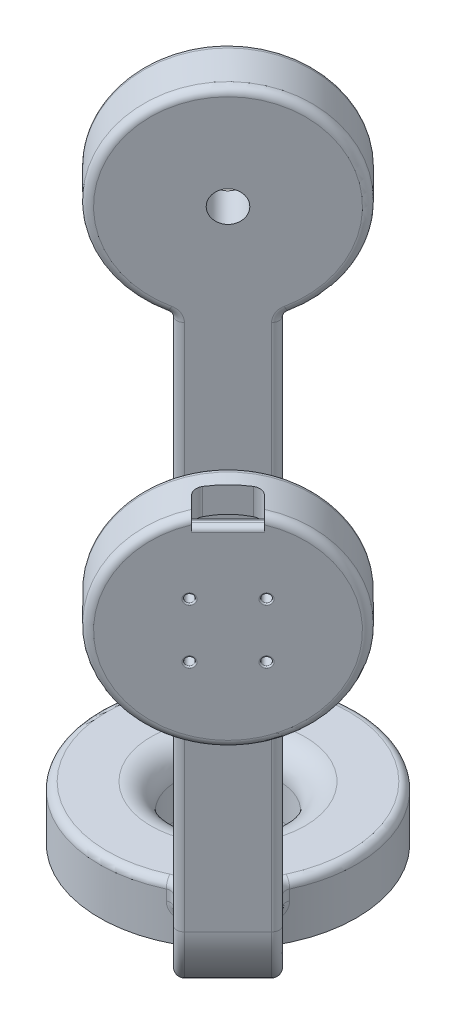
SolidWorks part; units mm, degrees
ref_plane "前视基准面" through (0, 0, 0) normal (0, 0, 1) x (1, 0, 0)
ref_plane "上视基准面" through (0, 0, 0) normal (0, 1, 0) x (1, 0, 0)
ref_plane "右视基准面" through (0, 0, 0) normal (1, 0, 0) x (0, 0, -1)
other "Configuration Table"
sketch "草图2" plane through (0, 0, 0) normal (0, 0, 1) x (1, 0, 0)
  line L2 (33, -6) -> (50, -6)
  line L3 (50, -6) -> (50, 5)
  line L9 (50, 5) -> (50, 14)
  line L10 (50, 14) -> (30, 14)
  line L15 (0, -22) -> (25, -22)
  line L17 (25, -22) -> (27, -22)
  line L18 (30, -19) -> (30, -9)
  line L19 (0, -22) -> (0, -12)
  line L20 (0, -12) -> (17, -12)
  line L21 (30, -9) -> (30, -6)
  line L22 (30, -6) -> (33, -6)
  line L23 (20, 4) -> (20, -9)
  arc A0 (27, -22) -> (30, -19) centre (27, -19) ccw
  arc A3 (20, -9) -> (17, -12) centre (17, -9) cw
  arc A4 (30, 14) -> (20, 4) centre (30, 4) ccw
  dimension "D1" = 3
  dimension "D2" = 10
revolve "旋转1" add sketch "草图2" angle 360 about L19
sketch "草图3" plane through (0, 0, 0) normal (0, -1, 0) x (1, 0, 0)
  circle A0 centre (12.5, 0) radius 1.6
  circle A1 centre (0, -12.5) radius 1.6
  circle A2 centre (-12.5, 0) radius 1.6
  circle A3 centre (0, 12.5) radius 1.6
  point P13 (0, 0)
  dimension "D1" = 4
extrude "切除-拉伸1" cut sketch "草图3" along normal blind 94
sketch "草图6" plane through (0, 0, 0) normal (-0.7071, 0, 0.7071) x (0.7071, 0, 0.7071)
  line L0 (30, 14) -> (30, 4)
  line L1 (0, 0) -> (0, 30.9502)
  line L3 (-30, 14) -> (-30, 4)
  line L5 (50, 14) -> (70, 14)
  line L8 (90, 34) -> (90, 114)
  line L13 (50, 14) -> (30, 14)
  line L17 (90, 114) -> (100, 114)
  line L18 (100, 114) -> (100, 34)
  line L19 (70, 4) -> (30, 4)
  line L20 (-50, 14) -> (-30, 14)
  line L21 (-70, 4) -> (-30, 4)
  line L22 (-50, 14) -> (-70, 14)
  line L23 (-90, 34) -> (-90, 114)
  line L24 (-90, 114) -> (-100, 114)
  line L25 (-100, 114) -> (-100, 34)
  arc A0 (90, 34) -> (70, 14) centre (70, 34) cw
  arc A2 (100, 34) -> (70, 4) centre (70, 34) cw
  arc A3 (-90, 34) -> (-70, 14) centre (-70, 34) ccw
  arc A4 (-100, 34) -> (-70, 4) centre (-70, 34) ccw
  dimension "D1" = 20
  dimension "D2" = 30
  dimension "D3" = 20
  dimension "D4" = 40
  dimension "D5" = 80
sketch "草图7" plane through (0, 0, 0) normal (-0.7071, 0, 0.7071) x (0.7071, 0, 0.7071)
  line L10 (90, 114) -> (103, 114)
  line L11 (103, 114) -> (103, 119)
  line L12 (103, 119) -> (107, 119)
  line L13 (107, 119) -> (107, 144)
  line L14 (107, 144) -> (112, 144)
  line L15 (112, 144) -> (112, 104)
  line L16 (90, 114) -> (90, 104)
  line L17 (112, 104) -> (90, 104)
  line L18 (0, 30.9502) -> (0, 0)
  line L19 (-90, 114) -> (-90, 104)
  line L20 (-112, 104) -> (-90, 104)
  line L21 (-112, 144) -> (-112, 104)
  line L22 (-107, 144) -> (-112, 144)
  line L27 (-107, 144) -> (-90, 144)
  line L28 (-90, 144) -> (-90, 114)
revolve "旋转2" add sketch "草图7" angle 360 about L14 region at (73.8745, 117.0769, 73.8745)
sketch "草图8" plane through (75.6604, 0, 75.6604) normal (-0.7071, 0, -0.7071) x (-0.7071, 0, 0.7071)
  circle A0 centre (10.6066, 154.6066) radius 1.6
  circle A1 centre (10.6066, 133.3934) radius 1.6
  circle A2 centre (-10.6066, 133.3934) radius 1.6
  circle A3 centre (-10.6066, 154.6066) radius 1.6
  point P13 (0, 144)
  dimension "D2" = 3.2
  dimension "D3" = 4
extrude "切除-拉伸3" cut sketch "草图8" against normal blind 30
fillet "圆角5" radius 0.5 4 edges at (85.5646, 133.3934, 72.8273) (70.5646, 133.3934, 87.8273) (70.5646, 154.6066, 87.8273) (85.5646, 154.6066, 72.8273)
fillet "圆角7" radius 1 2 edges at (51.6188, 144, 94.0452) (55.1543, 144, 90.5097)
sketch "草图9" plane through (75.6604, 0, 75.6604) normal (-0.7071, 0, -0.7071) x (-0.7071, 0, 0.7071)
  line L0 (0, 144) -> (19.5212, 144)
ref_plane "基准面3" through (0, 144, 0) normal (0, -1, 0) x (-0.7071, 0, 0.7071)
sketch "草图10" plane through (0, 144, 0) normal (0, -1, 0) x (-0.7071, 0, 0.7071)
  line L0 (0, -107) -> (10, -107)
  line L1 (0, -107) -> (19.5212, -107) construction
  line L2 (10, -107) -> (10, -102)
  line L3 (7, -99) -> (-7, -99)
  line L4 (-10, -102) -> (-10, -107)
  line L5 (-10, -107) -> (0, -107)
  arc A0 (-7, -99) -> (-10, -102) centre (-7, -102) ccw
  arc A1 (7, -99) -> (10, -102) centre (7, -102) cw
  dimension "D1" = 3
extrude "切除-拉伸4" cut sketch "草图10" against normal blind 225
sketch "草图11" plane through (75.6604, 0, 75.6604) normal (-0.7071, 0, -0.7071) x (-0.7071, 0, 0.7071)
  line L0 (-10, 179) -> (-10, 182.7298)
  line L1 (-10, 179) -> (10, 179)
  line L2 (10, 182.7298) -> (10, 166.9129) construction
  line L3 (10, 179) -> (10, 182.7298)
  arc A0 (10, 182.7298) -> (-10, 182.7298) centre (0, 144) ccw
extrude "切除-拉伸5" cut sketch "草图11" against normal blind 225
fillet "圆角8" radius 2 1 edges at (75.6604, 179, 75.6604)
fillet "圆角9" radius 2 1 edges at (79.196, 179, 79.196)
revolve "旋转3" add sketch "草图7<3>" angle 360 about L22 region at (-71.4178, 124, -71.4178)
sketch "草图7<3>" plane through (0, 0, 0) normal (-0.7071, 0, 0.7071) x (0.7071, 0, 0.7071) same geometry as "草图7"
sketch "草图12" plane through (-79.196, 0, -79.196) normal (-0.7071, 0, -0.7071) x (-0.7071, 0, 0.7071)
  line L0 (0, 144) -> (0, 104) construction
  line L1 (-42.1172, 144) -> (42.1172, 144) construction
  circle A0 centre (0, 144) radius 16.5
extrude "切除-拉伸6" cut sketch "草图12" against normal blind 6
sketch "草图13" plane through (-74.9533, 0, -74.9533) normal (-0.7071, 0, -0.7071) x (-0.7071, 0, 0.7071)
  circle A0 centre (0, 144) radius 6
extrude "切除-拉伸7" cut sketch "草图13" against normal blind 45
sketch "草图14" plane through (-74.9533, 0, -74.9533) normal (-0.7071, 0, -0.7071) x (-0.7071, 0, 0.7071)
  line L0 (0, 144) -> (0, 155.5)
  circle A0 centre (0, 155.5) radius 1.4
  circle A1 centre (11.5, 144) radius 1.4
  circle A2 centre (0, 132.5) radius 1.4
  circle A3 centre (-11.5, 144) radius 1.4
  point P14 (0, 144)
  dimension "D1" = 4
extrude "切除-拉伸8" cut sketch "草图14" against normal blind 6 contours A1 | A2 | A3 | A0
chamfer "倒角1" distance 0.5 angle 45 4 edges at (-84.075, 144, -65.8316) (-75.9433, 132.5, -73.9634) (-67.8115, 144, -82.0951) (-75.9433, 155.5, -73.9634)
fillet "圆角13" radius 1 1 edges at (-90.8632, 144, -67.5287)
extrude "凸台-拉伸1" add sketch "草图6" along normal mid plane 30 contours A2 L18 L17 L8 A0 L5 L13 L0 L19 | L23 L24 L25 A4 L21 L3 L20 L22 A3 region at (28.2843, 12.6962, 28.2843)
sketch "草图15" plane through (0, -12, 0) normal (0, 1, 0) x (1, 0, 0)
  line L0 (0, 0) -> (21.2132, -21.2132)
  line L1 (49.4975, -49.4975) -> (21.2132, -21.2132) construction
  line L2 (-38.8909, 38.8909) -> (38.8909, -38.8909) construction
sketch "草图16" plane through (0, -6, 0) normal (0, -1, 0) x (-1, 0, 0)
  line L1 (-35.3553, -35.3553) -> (-21.2132, -21.2132) construction
  circle A0 centre (-28.2843, -28.2843) radius 4
  circle A1 centre (-40, 0) radius 4
  circle A2 centre (-28.2843, 28.2843) radius 4
  circle A3 centre (0, 40) radius 4
  circle A4 centre (28.2843, 28.2843) radius 4
  circle A5 centre (40, 0) radius 4
  circle A6 centre (28.2843, -28.2843) radius 4
  circle A7 centre (0, -40) radius 4
  point P22 (0, 0)
  dimension "D1" = 8
extrude "切除-拉伸9" cut sketch "草图16" against normal blind 10
chamfer "倒角3" distance 0.5 angle 45 4 edges at (-1.6, -12, 12.5) (10.9, -12, 0) (-14.1, -12, 0) (-1.6, -12, -12.5)
fillet "圆角14" radius 3 43 edges at (77.7817, 106.919, 56.5685) (-60.1041, 70.4595, -81.3173) (-53.8909, 12.7868, -75.1041) (-81.3173, 70.4595, -60.1041) (-75.1041, 12.7868, -53.8909) (-74.2462, 70.4595, -53.033) (-70.1041, 19.8579, -48.8909) (-53.033, 70.4595, -74.2462) (-48.8909, 19.8579, -70.1041) (60.1041, 70.4595, 81.3173) (53.8909, 12.7868, 75.1041) (53.033, 70.4595, 74.2462) (48.8909, 19.8579, 70.1041) (81.3173, 70.4595, 60.1041) (75.1041, 12.7868, 53.8909) (74.2462, 70.4595, 53.033) (70.1041, 19.8579, 48.8909) (-77.7817, 106.919, -56.5685) (-56.5685, 106.919, -77.7817) (-70.7107, 104, -70.7107) (70.7107, 104, 70.7107) (79.196, 104, 79.196) (42.4264, 144, 84.8528) (56.5685, 106.919, 77.7817) (63.6396, 184, 63.6396) (-63.6396, 184, -63.6396) (-50.9117, 144, -107.4802) (44.3334, 9, 23.1202) (35.3553, 4, 35.3553) (23.1202, 9, 44.3334) (-44.3334, 9, -23.1202) (-35.3553, 4, -35.3553) (-23.1202, 9, -44.3334) (-31.0056, 4, -52.2188) (-52.2188, 4, -31.0056) (-52.2188, 14, -31.0056) (-31.0056, 14, -52.2188) (35.3553, 14, -35.3553) (-35.3553, 14, 35.3553) (31.0056, 4, 52.2188) (31.0056, 14, 52.2188) (52.2188, 4, 31.0056) (52.2188, 14, 31.0056)
sketch "草图17" plane through (0, -6, 0) normal (0, -1, 0) x (1, 0, 0)
  circle A0 centre (0, 0) radius 30
  circle A1 centre (0, 0) radius 50
  circle A2 centre (40, 0) radius 4
  circle A3 centre (28.2843, -28.2843) radius 4
  circle A4 centre (0, -40) radius 4
  circle A5 centre (-28.2843, -28.2843) radius 4
  circle A6 centre (-40, 0) radius 4
  circle A7 centre (-28.2843, 28.2843) radius 4
  circle A8 centre (0, 40) radius 4
  circle A9 centre (28.2843, 28.2843) radius 4
  point P23 (0, 0)
  dimension "D1" = 8
extrude "凸台-拉伸2" add sketch "草图17" along normal blind 1
chamfer "倒角4" distance 0.5 angle 45 8 edges at (-24.2843, -7, -28.2843) (4, -7, -40) (32.2843, -7, -28.2843) (44, -7, 0) (32.2843, -7, 28.2843) (4, -7, 40) (-24.2843, -7, 28.2843) (-36, -7, 0)
